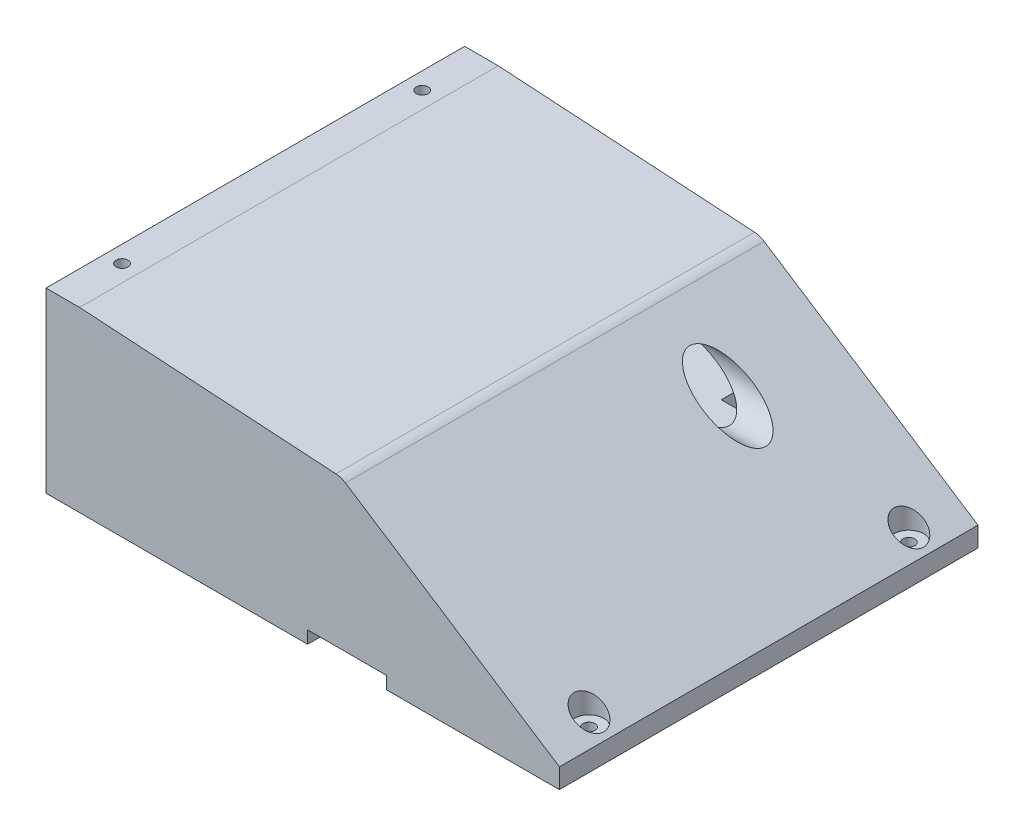
SolidWorks part; units mm, degrees
ref_plane "Front Plane" through (0, 0, 0) normal (0, 0, 1) x (1, 0, 0)
ref_plane "Top Plane" through (0, 0, 0) normal (0, 1, 0) x (1, 0, 0)
ref_plane "Right Plane" through (0, 0, 0) normal (1, 0, 0) x (0, 0, -1)
sketch "Sketch1" plane through (0, 0, 0) normal (0, 0, 1) x (1, 0, 0)
  line L0 (0, 0) -> (-20, 0)
  line L3 (-242.9846, 20) -> (-242.9846, 25)
  line L4 (-242.9846, 25) -> (-260, 25)
  line L5 (-260, 25) -> (-260, 30)
  line L10 (-242.9846, 85) -> (-260, 85)
  line L11 (-260, 85) -> (-260, 90)
  line L14 (-242.9846, 90) -> (-260, 90)
  line L23 (-49.1581, 30) -> (-260, 30)
  line L26 (-49.1581, 30) -> (-122.3017, 77.5)
  line L27 (-260, 30) -> (-120, 30) construction
  line L28 (-260, 30) -> (-260, 67) construction
  line L29 (-260, 67) -> (-120, 67) construction
  line L30 (-120, 30) -> (-120, 67) construction
  line L31 (-110.512, 81.7673) -> (0, 10)
  line L32 (-20, 0) -> (-20, 20)
  line L35 (0, 0) -> (0, 10)
  line L36 (-242.9846, 20) -> (-20, 20)
  line L37 (-242.9846, 85) -> (-122.3017, 77.5)
  line L38 (-242.9846, 90) -> (-110.512, 81.7673)
  dimension "D1" = 20
  dimension "D2" = 20
  dimension "D3" = 10
  dimension "D4" = 55
  dimension "D5" = 5
  dimension "D6" = 140
  dimension "D7" = 37
  dimension "D9" = 33
  dimension "D10" = 10
  dimension "D11" = 260
  dimension "D13" = 222.9846
extrude "Boss-Extrude1" add sketch "Sketch1" along normal blind 212
sketch "Sketch2" plane through (0, 0, 0) normal (0, 0, -1) x (-1, 0, 0)
  line L2 (0, 0) -> (260, 0)
  line L3 (260, 0) -> (260, 90)
  line L5 (110.512, 81.7673) -> (0, 10)
  line L6 (0, 10) -> (0, 0)
  line L7 (260, 90) -> (110.512, 81.7673)
extrude "Boss-Extrude2" add sketch "Sketch2" against normal blind 10
sketch "Sketch3" plane through (0, 0, 212) normal (0, 0, 1) x (1, 0, 0)
  line L1 (-110.512, 81.7673) -> (0, 10)
  line L2 (0, 10) -> (0, 0)
  line L3 (0, 0) -> (-260, 0)
  line L4 (-260, 0) -> (-260, 90)
  line L5 (-260, 90) -> (-110.512, 81.7673)
extrude "Boss-Extrude3" add sketch "Sketch3" against normal blind 10
sketch "Sketch4" plane through (0, 0, 0) normal (0, -1, 0) x (1, 0, 0)
  line L0 (0, 212) -> (0, 0) construction
  line L4 (-260, 212) -> (0, 212) construction
  line L5 (0, 106) -> (-20, 106) construction
  line L6 (-20, 202) -> (-20, 10) construction
  circle A0 centre (-10, 187) radius 3
  circle A1 centre (-10, 25) radius 3
  dimension "D1" = 6
  dimension "D2" = 10
  dimension "D3" = 25
extrude "Cut-Extrude1" cut sketch "Sketch4" against normal through all
ref_plane "Plane1" through (0, 10, 0) normal (0, -1, 0) x (-1, 0, 0)
sketch "Sketch6" plane through (0, 10, 0) normal (0, -1, 0) x (-1, 0, 0)
  line L0 (0, -106) -> (20, -106) construction
  line L1 (0, -212) -> (0, 0) construction
  line L2 (20, -202) -> (20, -10) construction
  circle A0 centre (10, -25) radius 7.5
  circle A1 centre (10, -187) radius 7.5
  dimension "D1" = 15
extrude "Cut-Extrude2" cut sketch "Sketch6" against normal through all
sketch "Sketch7" plane through (0, 20, 0) normal (0, -1, 0) x (1, 0, 0)
  line L0 (-242.9846, 106) -> (-102.9846, 106) construction
  line L1 (-242.9846, 202) -> (-242.9846, 10) construction
  line L2 (-242.9846, 166) -> (-102.9846, 166) construction
  line L3 (-242.9846, 166) -> (-242.9846, 46) construction
  line L4 (-242.9846, 46) -> (-102.9846, 46) construction
  line L5 (-102.9846, 166) -> (-102.9846, 46) construction
  line L7 (-20, 10) -> (-260, 10) construction
  line L8 (-260, 202) -> (-20, 202) construction
  line L9 (-97.0991, 166) -> (-87.0991, 166)
  line L10 (-97.0991, 166) -> (-97.0991, 46)
  line L11 (-97.0991, 46) -> (-87.0991, 46)
  line L12 (-87.0991, 166) -> (-87.0991, 46)
  line L13 (-100, 30) -> (-40, 30)
  line L14 (-100, 30) -> (-100, 15)
  line L15 (-100, 15) -> (-40, 15)
  line L16 (-40, 30) -> (-40, 15)
  line L17 (-20, 202) -> (-20, 10) construction
  circle A0 centre (-161.4846, 161) radius 1.5
  circle A1 centre (-225.6846, 161) radius 1.5
  circle A2 centre (-161.4846, 51) radius 1.5
  circle A3 centre (-225.6846, 51) radius 1.5
  circle A4 centre (-67.9846, 136) radius 12.5
  dimension "D4" = 3
  dimension "D6" = 3
  dimension "D9" = 25
  dimension "D1" = 120
  dimension "D2" = 140
  dimension "D3" = 36
  dimension "D5" = 58.5
  dimension "D7" = 122.7
  dimension "D8" = 5
  dimension "D10" = 30
  dimension "D11" = 35
  dimension "D12" = 10
  dimension "D13" = 120
  dimension "D14" = 15
  dimension "D15" = 60
  dimension "D16" = 5
  dimension "D17" = 20
extrude "Cut-Extrude3" cut sketch "Sketch7" against normal blind 12.5
ref_plane "Plane2" through (-110.512, 0, 0) normal (-1, 0, 0) x (0, 0, 1)
sketch "Sketch8" plane through (-110.512, 0, 0) normal (-1, 0, 0) x (0, 0, 1)
  line L0 (202, 30) -> (30, 30) construction
  circle A0 centre (54, 57.25) radius 12.5
  point P4 (116, 30)
  dimension "D3" = 25
  dimension "D1" = 27.25
  dimension "D2" = 62
extrude "Cut-Extrude4" cut sketch "Sketch8" against normal up to next
sketch "Sketch9" plane through (0, 25, 0) normal (0, -1, 0) x (1, 0, 0)
  line L0 (-242.9846, 202) -> (-260, 202) construction
  line L1 (-260, 202) -> (-260, 10) construction
  line L2 (-242.9846, 106) -> (-260, 106) construction
  line L3 (-242.9846, 202) -> (-242.9846, 10) construction
  circle A0 centre (-251.5, 182) radius 3
  circle A1 centre (-251.5, 30) radius 3
  dimension "D1" = 20
  dimension "D3" = 6
  dimension "D2" = 8.5
extrude "Cut-Extrude5" cut sketch "Sketch9" against normal through all both and the other way through all
sketch "Sketch10" plane through (0, 0, 212) normal (0, 0, 1) x (1, 0, 0)
  line L0 (-260, 0) -> (0, 0) construction
  line L1 (-127.5, 0) -> (-87.5, 0)
  line L2 (-127.5, 0) -> (-127.5, 6.35)
  line L3 (-127.5, 6.35) -> (-87.5, 6.35)
  line L4 (-87.5, 0) -> (-87.5, 6.35)
  line L5 (0, 0) -> (0, 10) construction
  dimension "D1" = 87.5
  dimension "D2" = 40
  dimension "D3" = 6.35
extrude "Cut-Extrude6" cut sketch "Sketch10" against normal through all both
fillet "Fillet1" radius 10 1 edges at (-110.512, 81.7673, 106)
